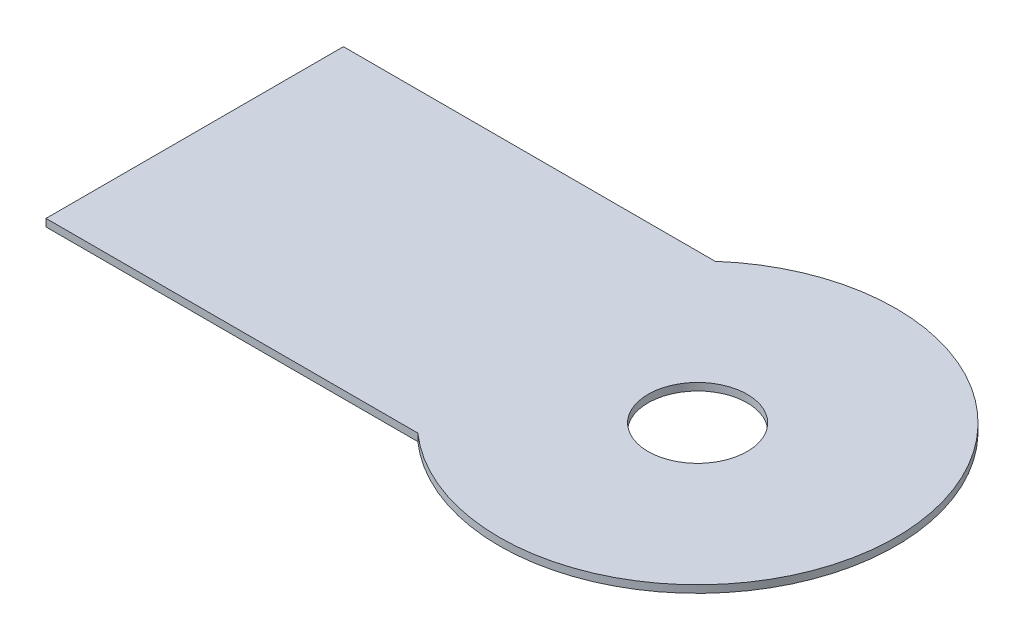
SolidWorks part; units mm, degrees
ref_plane "Front Plane" through (0, 0, 0) normal (0, 0, 1) x (1, 0, 0)
ref_plane "Top Plane" through (0, 0, 0) normal (0, 1, 0) x (1, 0, 0)
ref_plane "Right Plane" through (0, 0, 0) normal (1, 0, 0) x (0, 0, -1)
sketch "Sketch1" plane through (0, 0, 0) normal (0, 1, 0) x (1, 0, 0)
  line L0 (122.915, 60) -> (150, 60) construction
  line L1 (0, 0) -> (150, 0)
  line L2 (0, 0) -> (0, 120)
  line L3 (0, 120) -> (150, 120)
  arc A0 (150, 0) -> (150, 120) centre (202.915, 60) ccw
  circle A1 centre (202.915, 60) radius 20
  dimension "D4" = 160
  dimension "D3" = 40
  dimension "D1" = 150
  dimension "D2" = 120
  dimension "D5" = 52.915
base flange "Base-Flange1" sketch "Sketch1" thickness 3 reverse thickness direction no parameters "D1"=1.5875
sketch "Bend-Lines1" [suppressed] plane through (0, 0, 0) normal (0, 1, 0) x (1, 0, 0)
sketch "Bounding-Box1" [suppressed] plane through (0, 0, 0) normal (0, 1, 0) x (1, 0, 0)
sheet metal parameters "Sheet-Metal1" thickness 3 parameters "D1"=1.5875
flat pattern "Flat-Pattern1" [suppressed]
sketch "Bend-Lines2" plane through (0, 0, 0) normal (0, 1, 0) x (1, 0, 0)
sketch3d "Bounding-Box2" [suppressed]
  line L0 (-80, -80, 0) -> (202.915, -80, 0) construction
  line L1 (-80, 80, 0) -> (202.915, 80, 0) construction
  line L2 (-80, -80, 0) -> (-80, 80, 0) construction
  line L3 (202.915, -80, 0) -> (202.915, 80, 0) construction
